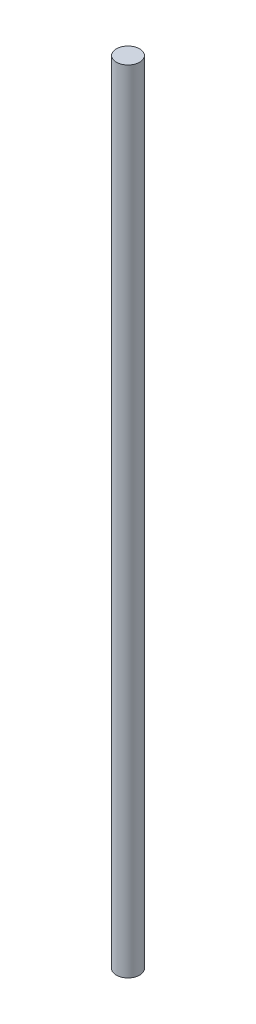
SolidWorks part; units mm, degrees
ref_plane "Front Plane" through (0, 0, 0) normal (0, 0, 1) x (1, 0, 0)
ref_plane "Top Plane" through (0, 0, 0) normal (0, 1, 0) x (1, 0, 0)
ref_plane "Right Plane" through (0, 0, 0) normal (1, 0, 0) x (0, 0, -1)
sketch "Sketch1" plane through (0, 0, 0) normal (0, 1, 0) x (1, 0, 0)
  circle A0 centre (0, 0) radius 12.5
  dimension "D1" = 25
extrude "Boss-Extrude1" add sketch "Sketch1" along normal blind 850
